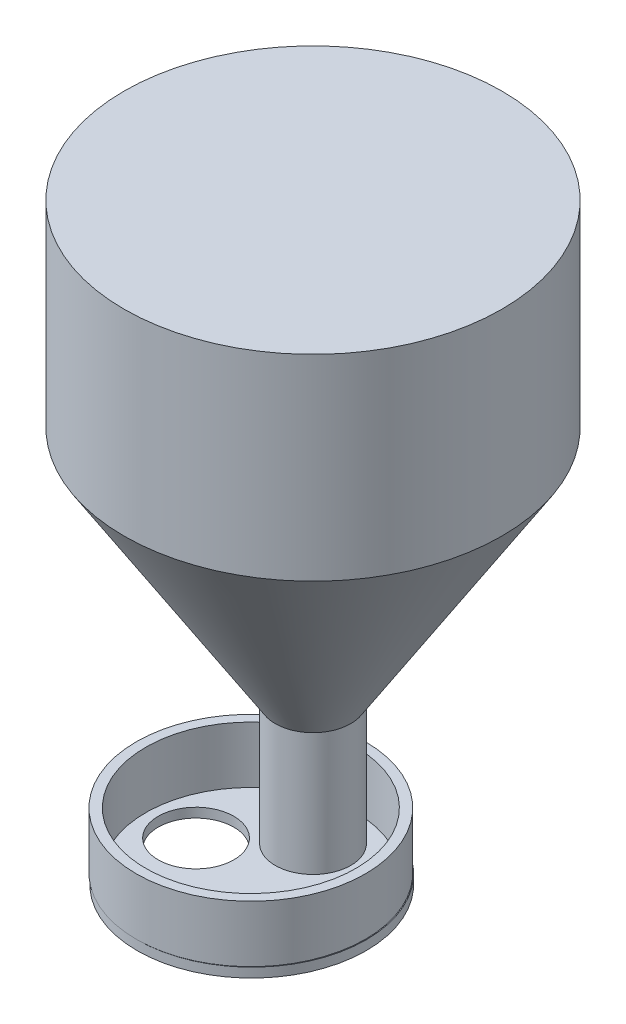
SolidWorks part; units mm, degrees
ref_plane "Alzado" through (0, 0, 0) normal (0, 0, 1) x (1, 0, 0)
ref_plane "Planta" through (0, 0, 0) normal (0, 1, 0) x (1, 0, 0)
ref_plane "Vista lateral" through (0, 0, 0) normal (1, 0, 0) x (0, 0, -1)
sketch "Croquis1" plane through (0, 0, 0) normal (0, 1, 0) x (1, 0, 0)
  circle A0 centre (0, 0) radius 100
  dimension "D1" = 200
ref_plane "Plano1" through (0, -230, 0) normal (0, 1, 0) x (1, 0, 0)
extrude "Saliente-Extruir1" add sketch "Croquis1" against normal blind 104 contours A0
sketch "Croquis2" plane through (0, -104, 0) normal (0, -1, 0) x (1, 0, 0)
  circle A2 centre (0, 0) radius 100
sketch "Croquis3" plane through (0, -230, 0) normal (0, 1, 0) x (1, 0, 0)
  circle A0 centre (0, 0) radius 20
  dimension "D1" = 40
loft "Recubrir1" add profiles "Croquis3", "Croquis2" connector at (-19.9701, -230, 1.0927) connector at (-99.8027, -104, 6.2791)
sketch "Croquis4" plane through (0, -230, 0) normal (0, -1, 0) x (1, 0, 0)
  circle A0 centre (0, 0) radius 20
  dimension "D1" = 40
extrude "Saliente-Extruir2" add sketch "Croquis4" along normal blind 65
ref_plane "Plano2" through (0, 0, -20) normal (0, 0, -1) x (-1, 0, 0)
sketch "Croquis7" plane through (0, -295, 0) normal (0, -1, 0) x (1, 0, 0)
  circle A0 centre (0, 0) radius 17.5
  dimension "D1" = 35
extrude "Cortar-Extruir2" cut sketch "Croquis7" against normal blind 24
sketch "Croquis8" plane through (0, -295, 0) normal (0, -1, 0) x (1, 0, 0)
  circle A0 centre (-32.8935, 0) radius 60.6028
  circle A1 centre (-32.8935, 0) radius 55.6028
  dimension "D1" = 5
extrude "Saliente-Extruir3" add sketch "Croquis8" along normal blind 30 separate body
sketch "Croquis9" plane through (0, -295, 0) normal (0, 1, 0) x (1, 0, 0)
  circle A0 centre (-32.4436, 0) radius 60.6028
sketch "Croquis10" plane through (0, -325, 0) normal (0, -1, 0) x (1, 0, 0)
  circle A0 centre (-32.4436, 0) radius 60.6028
  circle A1 centre (-63.5378, -1.6179) radius 20
  dimension "D1" = 40
extrude "Saliente-Extruir5" add sketch "Croquis10" along normal blind 5
